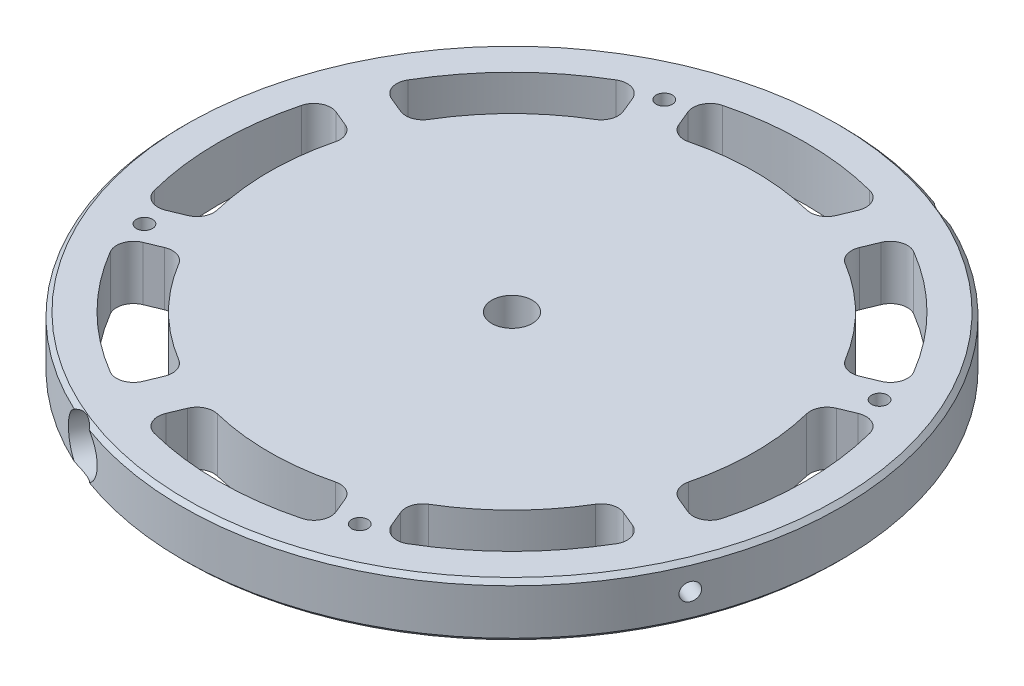
SolidWorks part; units mm, degrees
material "6061-T6 (SS)"
ref_plane "Front Plane" through (0, 0, 0) normal (0, 0, 1) x (1, 0, 0)
ref_plane "Top Plane" through (0, 0, 0) normal (0, 1, 0) x (1, 0, 0)
ref_plane "Right Plane" through (0, 0, 0) normal (1, 0, 0) x (0, 0, -1)
sketch "Sketch2" plane through (0, 0, 0) normal (1, 0, 0) x (0, 0, -1)
  line L0 (0, 0) -> (-77.55, 0)
  line L1 (-77.55, 0) -> (-77.55, 12.7)
  line L2 (-77.55, 12.7) -> (0, 12.7)
  line L5 (0, 12.7) -> (0, 0)
  dimension "D1" = 77.55
  dimension "D2" = 12.7
ref_axis "Axis1" through (0, -0.8888, 0) along (0, 1, 0)
revolve "Revolve1" add sketch "Sketch2" angle 360 about axis through (0, -0.8888, 0) along (0, 1, 0)
hole_wizard "#10-24 Tapped Hole2" positions "Sketch6" profile "Sketch7" tap size "#10-24" standard "ANSI Inch" end condition through all
sketch "Sketch6" plane through (0, 12.7, 0) normal (0, 1, 0) x (1, 0, 0)
  line L0 (0, 0) -> (-53.438, 129.0108) construction
  line L2 (0, 0) -> (0, 109.0908) construction
  point P0 (-25.3336, 61.1608)
  dimension "D1" = 22.5
  dimension "D2" = 66.2
sketch "Sketch7" plane through (-25.3336, 12.7, -61.1608) normal (1, 0, 0) x (0, 0, 1)
  line L0 (0, 0) -> (0, 12.7)
  line L1 (0, 12.7) -> (1.8986, 12.7)
  line L2 (1.8986, 12.7) -> (1.8986, 0)
  line L5 (1.8986, 0) -> (0, 0)
  line L11 (0, -6.35) -> (0, 107.95) construction
  dimension "Thread Major Dia." = 3.7973
  dimension "Thru Tap Drill Depth" = 12.7
pattern_circular "CirPattern3" count 4 over 360 about axis through (0, -0.8888, 0) along (0, 1, 0) of "#10-24 Tapped Hole2"
sketch "Sketch8" plane through (0, 12.7, 0) normal (0, 1, 0) x (1, 0, 0)
  line L4 (0, 0) -> (0, 93.9995) construction
  line L5 (0, 0) -> (113.8372, 0) construction
  line L6 (-17.1671, 54.5107) -> (-21.7355, 65.5398)
  line L7 (17.1671, 54.5107) -> (21.7355, 65.5398)
  line L8 (0, 0) -> (-25.3336, 61.1608) construction
  arc A0 (-17.1671, 54.5107) -> (17.1671, 54.5107) centre (0, 0) cw
  arc A1 (-21.7355, 65.5398) -> (21.7355, 65.5398) centre (0, 0) cw
  circle A2 centre (0, 0) radius 77.55 construction
  dimension "D1" = 57.15
  dimension "D2" = 8.5
  dimension "D3" = 5
extrude "Cut-Extrude1" cut sketch "Sketch8" against normal through all
fillet "Fillet1" radius 4 4 edges at (17.1671, 6.35, -54.5107) (21.7355, 6.35, -65.5398) (-17.1671, 6.35, -54.5107) (-21.7355, 6.35, -65.5398)
pattern_circular "CirPattern4" count 8 over 360 about axis through (0, -0.8888, 0) along (0, 1, 0) of "Cut-Extrude1", "Fillet1"
chamfer "Chamfer1" distance 1 angle 45 2 edges at (0, 0, -77.55) (0, 12.7, -77.55)
ref_plane "Plane1" through (0, 0, 0) normal (0.9239, 0, 0.3827) x (0, 1, 0)
hole_wizard "#20 (0.161) Diameter Hole1" positions "Sketch16" profile "Sketch15" hole size "#20" standard "ANSI Inch" end condition through all
sketch "Sketch16" plane through (0, 0, 0) normal (0.9239, 0, 0.3827) x (0, 1, 0)
  point P0 (6.35, 0)
  dimension "D1" = 6.35
sketch "Sketch15" plane through (0, 6.35, 0) normal (0, 1, 0) x (-0.3827, 0, 0.9239)
  line L0 (0, 0) -> (0, 101.324)
  line L1 (0, 101.324) -> (2.0447, 101.324)
  line L2 (2.0447, 101.324) -> (2.0447, 0)
  line L5 (2.0447, 0) -> (0, 0)
  line L11 (0, -6.35) -> (0, 107.95) construction
  dimension "Thru Hole Dia." = 4.0894
  dimension "Thru Hole Depth" = 101.324
ref_plane "Plane2" through (29.6771, 0, -71.6469) normal (0.3827, 0, -0.9239) x (-0.9239, 0, -0.3827)
sketch "Sketch19" plane through (29.6771, 0, -71.6469) normal (0.3827, 0, -0.9239) x (-0.9239, 0, -0.3827)
  line L0 (-76.55, 0) -> (76.55, 0) construction
  line L2 (0, -0.8888) -> (0, 13.5888) construction
  circle A0 centre (0, 6.35) radius 5.5625 construction
  circle A1 centre (0, 6.35) radius 6.25
  dimension "D1" = 12.5
  dimension "D2" = 6.35
extrude "Cut-Extrude3" cut sketch "Sketch19" against normal blind 5
pattern_circular "CirPattern5" count 2 over 360 about axis through (0, -0.8888, 0) along (0, 1, 0) of "Cut-Extrude3"
hole_wizard "#10-24 Tapped Hole1" positions "Sketch20" profile "Sketch21" tap size "#10-24" standard "ANSI Inch"
sketch "Sketch20" plane through (-27.7637, 0, 67.0275) normal (-0.3827, 0, 0.9239) x (0.9239, 0, 0.3827)
  circle A0 centre (0, 6.35) radius 6.25
  circle A1 centre (0, 6.35) radius 6.25 construction
  point P0 (0, 6.35)
sketch "Sketch21" plane through (-27.7637, 6.35, 67.0275) normal (0, 1, 0) x (0.9239, 0, 0.3827)
  line L0 (0, 0) -> (0, 51.9408)
  line L1 (0, 51.9408) -> (1.8986, 50.8)
  line L2 (1.8986, 50.8) -> (1.8986, 0)
  line L5 (1.8986, 0) -> (0, 0)
  line L10 (0, 51.9408) -> (-1.8986, 50.8) construction
  line L11 (0, -6.35) -> (0, 107.95) construction
  dimension "Tap Drill Dia." = 3.7973
  dimension "Tap Drill Depth" = 50.8
  dimension "Drill Angle" = 118
pattern_circular "CirPattern6" count 2 over 360 about axis through (0, -0.8888, 0) along (0, 1, 0) of "#10-24 Tapped Hole1"
sketch "Sketch22" plane through (0, 12.7, 0) normal (0, 1, 0) x (1, 0, 0)
  circle A0 centre (0, 0) radius 4.765
  dimension "D1" = 9.53
extrude "Cut-Extrude4" cut sketch "Sketch22" against normal blind 12.8
equation "\"TubeDiameter\" = 6.500in"
equation "\"D1@Sketch2\"=(\"TubeDiameter\"/2)-5mm"
equation "\"D2@Sketch6\"=66.2"
